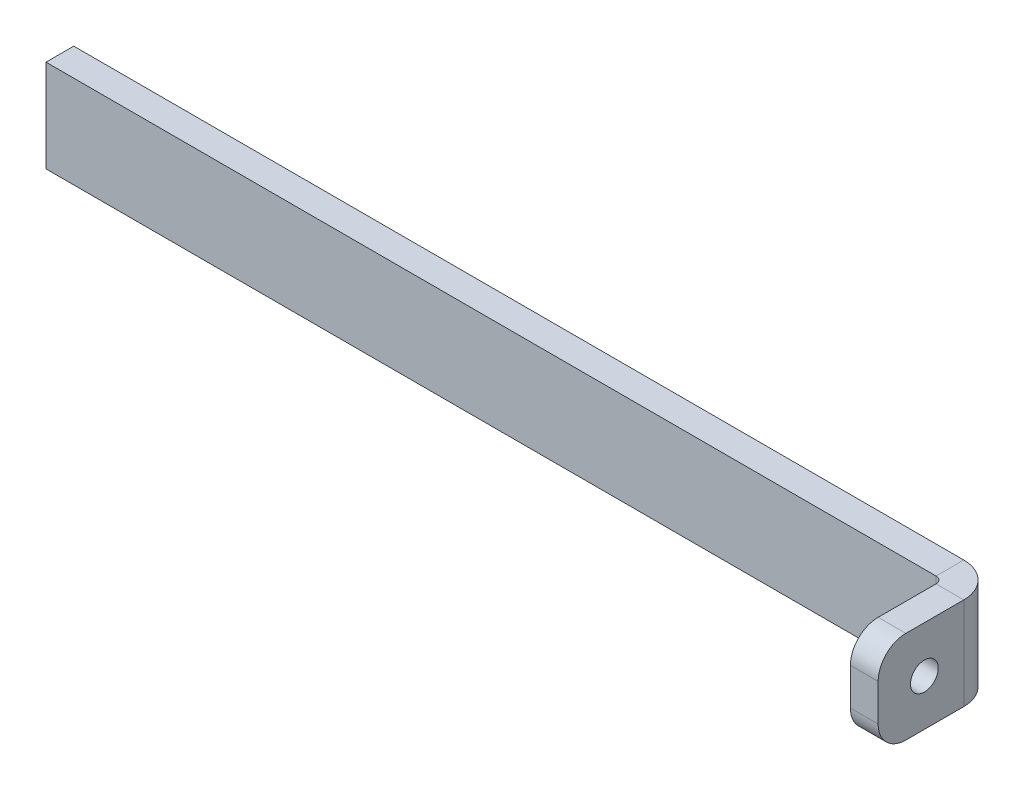
SolidWorks part; units mm, degrees
note: The reader was unsure of these and kept them because the rebuilt part matched: flange length of "边线-法兰1".
ref_plane "前视基准面" through (0, 0, 0) normal (0, 0, 1) x (1, 0, 0)
ref_plane "上视基准面" through (0, 0, 0) normal (0, 1, 0) x (1, 0, 0)
ref_plane "右视基准面" through (0, 0, 0) normal (1, 0, 0) x (0, 0, -1)
sketch "草图1" plane through (0, 0, 0) normal (0, 0, 1) x (1, 0, 0)
  line L1 (-50, -5) -> (50, -5)
  line L2 (-50, -5) -> (-50, 5)
  line L3 (-50, 5) -> (50, 5)
  line L4 (50, -5) -> (50, 5)
  line L5 (-50, -5) -> (50, 5) construction
  line L6 (-50, 5) -> (50, -5) construction
  point P0 (0, 0)
  dimension "D1" = 10
  dimension "D2" = 100
base flange "基体-法兰1" sketch "草图1" thickness 3 reverse thickness direction no parameters "D1"=0.7366
edge flange "边线-法兰1" sketch "草图8" flange angle 90 flange length 10 flange position material inside bend radius 0.7366 thickness 3 relief rectangular parameters "D6"=10
sketch "草图8" plane through (50, 0, 0) normal (1, 0, 0) x (0, 1, 0)
  line L0 (-5, 0) -> (5, 0) construction
  line L1 (-5, 0) -> (5, 0)
  line L2 (-5, 0) -> (-5, 10)
  line L3 (-5, 10) -> (5, 10)
  line L4 (5, 10) -> (5, 0)
bend "边线折弯1" bend radius 0.7366 bend angle 90 parameters "D5"=1
sketch "草图9" plane through (50, 0, 0) normal (1, 0, 0) x (0, 0, -1)
  line L0 (-0.7366, 5) -> (-10, 5) construction
  line L1 (-10, 5) -> (-10, -5) construction
  circle A0 centre (-5, 0) radius 1.5
  dimension "D1" = 3
  dimension "D2" = 5
  dimension "D3" = 5
extrude "切除-拉伸1" cut sketch "草图9" against normal blind 10 normal cut yes
fillet "圆角1" radius 3 2 edges at (48.5, 5, 10) (48.5, -5, 10)
sketch "折弯-线1" [suppressed] plane through (0, 0, 0) normal (0, 1, 0) x (1, 0, 0)
sketch "边界框1" [suppressed] plane through (0, 0, 0) normal (0, 1, 0) x (1, 0, 0)
sheet metal parameters "钣金1" thickness 3 parameters "D1"=0.7366
flat pattern "平板型式1" [suppressed]
sketch "折弯-线2" plane through (0, 0, 0) normal (0, 1, 0) x (1, 0, 0)
sketch3d "边界框2" [suppressed]
  line L0 (50, -5, 0) -> (-50, -5, 0) construction
  line L1 (50, 5, 0) -> (-50, 5, 0) construction
  line L2 (50, -5, 0) -> (50, 5, 0) construction
  line L3 (-50, -5, 0) -> (-50, 5, 0) construction
sheet metal parameters "钣金2" thickness 3 parameters "D1"=0.7366
flat pattern "平板型式1"
sketch "折弯-线2" plane through (0, 0, 0) normal (0, 0, 1) x (1, 0, 0)
  line L0 (48.02, -5) -> (48.02, 5) construction
  line L1 (48.02, -5) -> (48.02, 5) construction
sketch3d "边界框2" [suppressed]
  line L0 (-50, -5, 0) -> (59.04, -5, 0) construction
  line L1 (-50, 5, 0) -> (59.04, 5, 0) construction
  line L2 (-50, -5, 0) -> (-50, 5, 0) construction
  line L3 (59.04, -5, 0) -> (59.04, 5, 0) construction
bend of the flat pattern "展开-<边线折弯1>1"
sheet metal parameters "钣金3" thickness 3 parameters "D1"=0.7366
flat pattern "平板型式1"
sketch "折弯-线2" plane through (0, 0, 0) normal (0, 0, 1) x (1, 0, 0)
  line L0 (48.02, -5) -> (48.02, 5) construction
  line L1 (48.02, -5) -> (48.02, 5) construction
sketch3d "边界框2" [suppressed]
  line L0 (-50, -5, 0) -> (59.04, -5, 0) construction
  line L1 (-50, 5, 0) -> (59.04, 5, 0) construction
  line L2 (-50, -5, 0) -> (-50, 5, 0) construction
  line L3 (59.04, -5, 0) -> (59.04, 5, 0) construction
bend of the flat pattern "展开-<边线折弯1>1"
